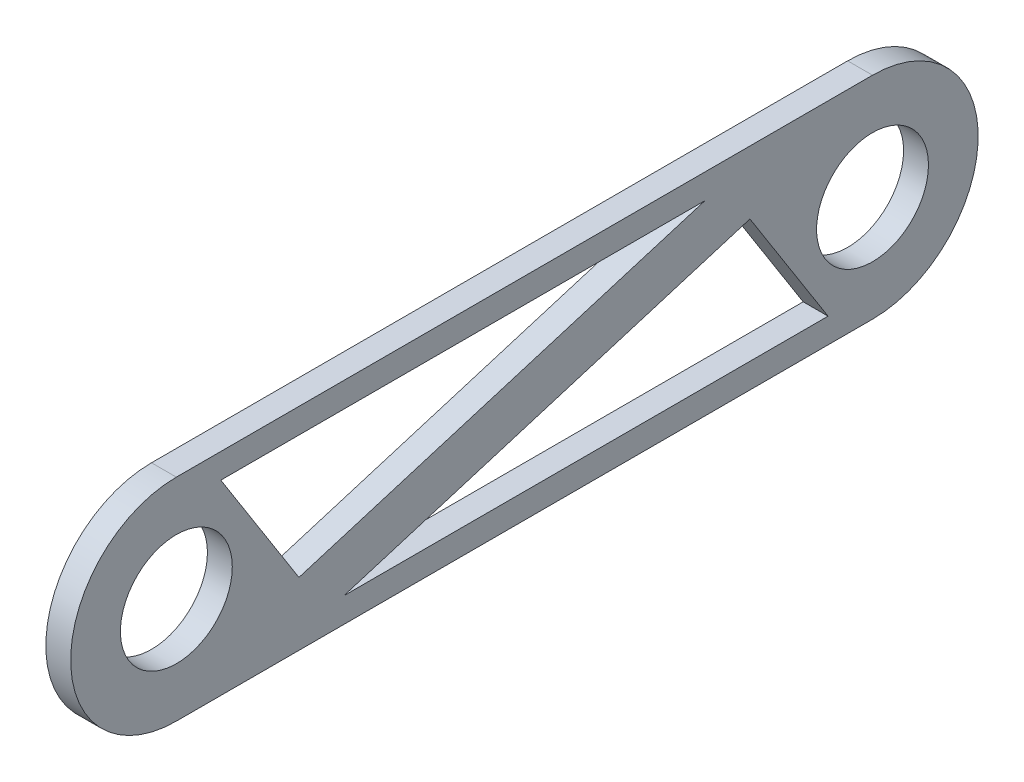
SolidWorks part; units mm, degrees
material "PC High Viscosity"
ref_plane "Front Plane" through (0, 0, 0) normal (0, 0, 1) x (1, 0, 0)
ref_plane "Top Plane" through (0, 0, 0) normal (0, 1, 0) x (1, 0, 0)
ref_plane "Right Plane" through (0, 0, 0) normal (1, 0, 0) x (0, 0, -1)
sketch "Sketch1" plane through (0, 0, 0) normal (1, 0, 0) x (0, 0, -1)
  line L0 (0, 26.9875) -> (177.8, 26.9875)
  line L1 (0, -26.9875) -> (177.8, -26.9875)
  line L2 (177.8, -26.9875) -> (177.8, 26.9875) construction
  line L3 (0, -26.9875) -> (177.8, 26.9875) construction
  line L4 (11.3512, 20.6375) -> (31.3126, -10.8457)
  line L5 (31.3126, -10.8457) -> (135.0221, 20.6375)
  line L6 (135.0221, 20.6375) -> (11.3512, 20.6375)
  line L7 (0, 26.9875) -> (177.8, -26.9875) construction
  line L8 (88.9, 0) -> (88.9, -26.9875) construction
  line L12 (88.9, 0) -> (-26.9875, 0) construction
  line L13 (166.4488, -20.6375) -> (146.4874, 10.8457)
  line L14 (42.7779, -20.6375) -> (166.4488, -20.6375)
  line L15 (146.4874, 10.8457) -> (42.7779, -20.6375)
  circle A0 centre (0, 0) radius 14.2875
  arc A1 (0, 26.9875) -> (0, -26.9875) centre (0, 0) ccw
  arc A2 (177.8, -26.9875) -> (177.8, 26.9875) centre (177.8, 0) ccw
  circle A3 centre (177.8, 0) radius 14.2875
  dimension "D1" = 28.575
  dimension "D2" = 12.7
  dimension "D5" = 28.575
  dimension "D3" = 177.8
  dimension "D4" = 177.8
  dimension "D6" = 6.35
  dimension "D7" = 6.35
  dimension "D8" = 20.6375
  dimension "D9" = 10.8457
extrude "Boss-Extrude1" add sketch "Sketch1" along normal blind 6.35 contours L1 A2 L0 A1 A3 L6 L5 L4 L15 L13 L14 A0 region at (0, 0, -88.9)
